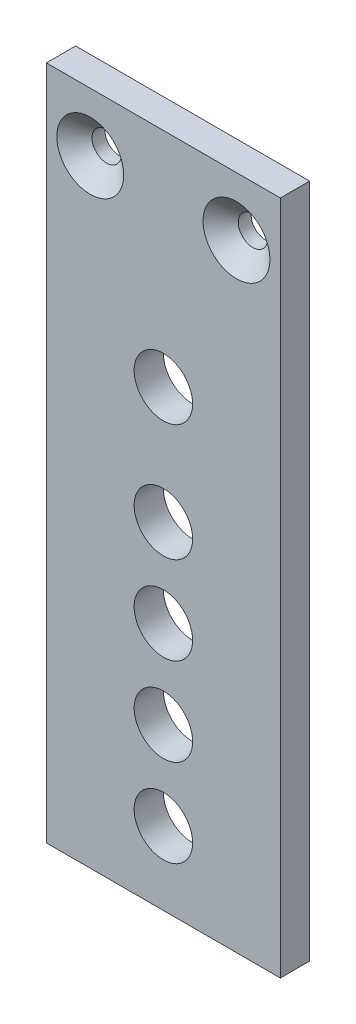
SolidWorks part; units mm, degrees
material "6061-T6 (SS)"
ref_plane "Front Plane" through (0, 0, 0) normal (0, 0, 1) x (1, 0, 0)
ref_plane "Top Plane" through (0, 0, 0) normal (0, 1, 0) x (1, 0, 0)
ref_plane "Right Plane" through (0, 0, 0) normal (1, 0, 0) x (0, 0, -1)
sketch "Sketch1" plane through (0, 0, 0) normal (0, 0, 1) x (1, 0, 0)
  line L0 (-25.4, -146.685) -> (25.4, -146.685)
  line L1 (-25.4, 0) -> (25.4, 0)
  line L2 (-25.4, 0) -> (-25.4, -146.685)
  line L4 (25.4, 0) -> (25.4, -146.685)
  circle A1 centre (0, -130.81) radius 6.35
  circle A2 centre (0, -111.76) radius 6.35
  circle A3 centre (0, -92.71) radius 6.35
  circle A4 centre (0, -73.66) radius 6.35
  circle A5 centre (-15.875, -12.7) radius 3.175
  circle A6 centre (15.875, -12.7) radius 3.175
  circle A7 centre (0, -48.26) radius 6.35
  point P18 (0, 0)
  dimension "D6" = 12.7
  dimension "D7" = 6.35
  dimension "D8" = 25.4
  dimension "D11" = 111.76
  dimension "D16" = 9.525
  dimension "D1" = 50.8
  dimension "D3" = 15.875
  dimension "D4" = 25.4
  dimension "D9" = 19.05
  dimension "D10" = 19.05
  dimension "D12" = 19.05
  dimension "D15" = 9.525
  dimension "D17" = 12.7
  dimension "D18" = 12.7
  dimension "D19" = 25.4
  dimension "D20" = 25.4
  dimension "D21" = 25.4
extrude "Boss-Extrude3" add sketch "Sketch1" along normal blind 6.35
chamfer "Chamfer1" distance 4.0894 angle 41 1 edges at (-12.7, -12.7, 6.35) first distance on face at (19.05, -12.7, 6.35)
chamfer "Chamfer2" distance 4.0894 angle 41 1 edges at (19.05, -12.7, 6.35) first distance on face at (-8.6106, -12.7, 6.35)
